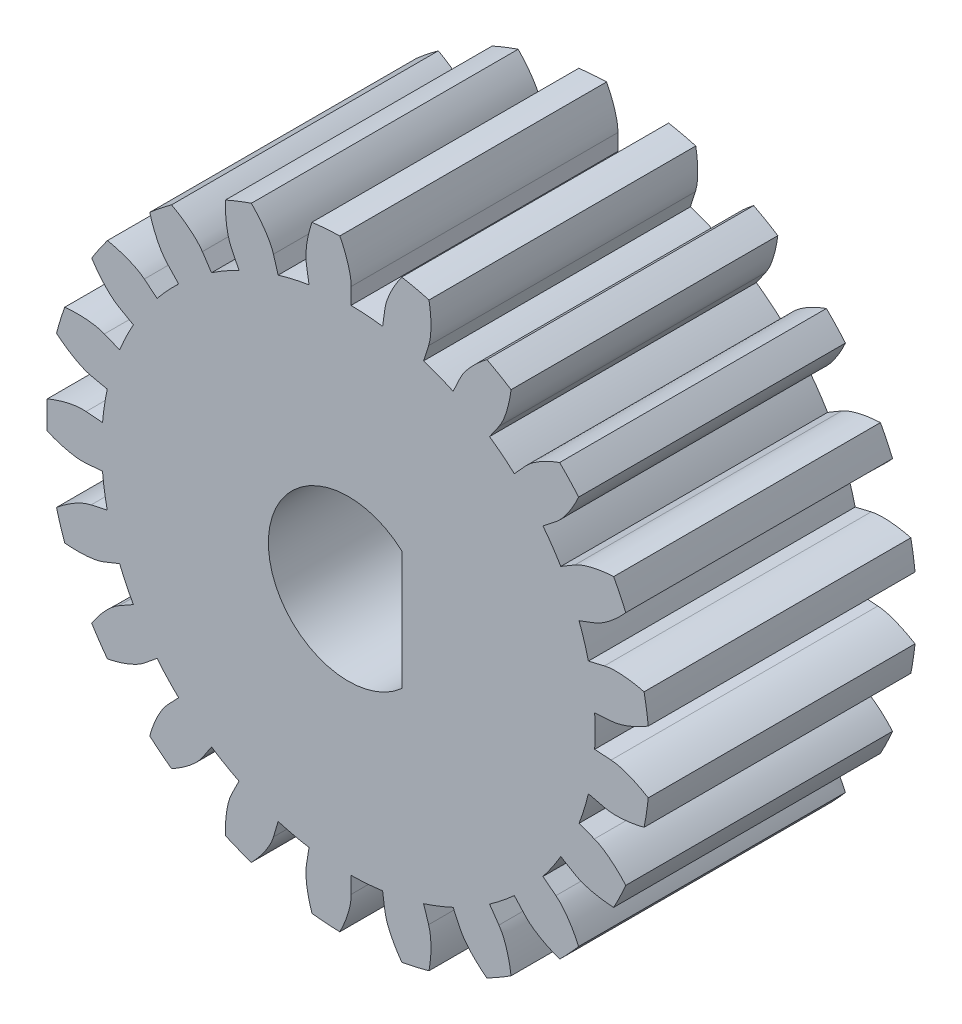
SolidWorks part; units mm, degrees
ref_plane "前视基准面" through (0, 0, 0) normal (0, 0, 1) x (1, 0, 0)
ref_plane "上视基准面" through (0, 0, 0) normal (0, 1, 0) x (1, 0, 0)
ref_plane "右视基准面" through (0, 0, 0) normal (1, 0, 0) x (0, 0, -1)
other "Configuration Table"
sketch "草图1" plane through (0, 0, 0) normal (0, 0, 1) x (1, 0, 0)
  line L0 (0, 0) -> (5.25, 0) construction
  line L1 (0, 0) -> (5.2353, 0.3923) construction
  line L2 (0, 0) -> (4.9232, 0.3169)
  line L3 (5.2353, 0.3923) -> (5.2353, -0.3923) construction
  line L4 (0, 0) -> (4.9232, -0.3169)
  circle A0 centre (0, 0) radius 5.75
  circle A1 centre (0, 0) radius 5.25 construction
  circle A2 centre (0, 0) radius 4.625
  circle A3 centre (0, 0) radius 4.9334 construction
  circle A4 centre (0, 0) radius 1.475
  spline S0 degree 4 poles (4.9232, 0.3169) (4.9607, 0.3193) (5.065, 0.3339) (5.2581, 0.3925) (5.555, 0.5296) (5.9082, 0.7653) (6.3141, 1.1289) (6.7208, 1.6221) (7.0851, 2.222) (7.4595, 3.0902) (7.6869, 4.0103) (7.7831, 4.9894) (7.7375, 6.1592) (7.5421, 7.3154) (7.1213, 8.6118) (6.437, 9.9622) (5.566, 11.1996) (4.5364, 12.3078) (3.3742, 13.2753) (2.1035, 14.0945) (0.7466, 14.7607) (-0.4976, 15.2081) (-1.5022, 15.4709) (-2.2418, 15.6171) (-2.7079, 15.6926) (-3.0798, 15.7435) (-3.4583, 15.7849) (-3.8273, 15.8169) (-4.1819, 15.8376) (-4.4716, 15.8494) (-4.8011, 15.8553) (-5.0151, 15.8558) (-5.3597, 15.8515) (-5.6291, 15.8407) (-5.9536, 15.8242) (-6.2447, 15.8018) (-6.5555, 15.7736) (-6.8526, 15.7397) (-7.0823, 15.71) (-7.2316, 15.6883) (-7.3069, 15.677) knots 0 0 0 0 0 0.005604 0.015718 0.02996 0.048734 0.068727 0.096889 0.125051 0.153212 0.209535 0.237696 0.271429 0.327752 0.384075 0.440398 0.496721 0.553044 0.609367 0.66569 0.722013 0.778336 0.806497 0.820578 0.834659 0.84874 0.86282 0.876901 0.890982 0.900036 0.909091 0.920455 0.931818 0.943182 0.954545 0.965909 0.977273 0.988636 1 1 1 1 1 construction
  spline S1 degree 4 poles (4.9232, 0.3169) (4.9607, 0.3193) (5.065, 0.3339) (5.2581, 0.3925) (5.555, 0.5296) (5.9082, 0.7653) (6.3141, 1.1289) (6.7208, 1.6221) (7.0851, 2.222) (7.4595, 3.0902) (7.6869, 4.0103) (7.7831, 4.9894) (7.7375, 6.1592) (7.5421, 7.3154) (7.1213, 8.6118) (6.437, 9.9622) (5.566, 11.1996) (4.5364, 12.3078) (3.3742, 13.2753) (2.1035, 14.0945) (0.7466, 14.7607) (-0.4976, 15.2081) (-1.5022, 15.4709) (-2.2418, 15.6171) (-2.7079, 15.6926) (-3.0798, 15.7435) (-3.4583, 15.7849) (-3.8273, 15.8169) (-4.1819, 15.8376) (-4.4716, 15.8494) (-4.7152, 15.8537) (-4.8263, 15.8548) (-4.8814, 15.855) knots 0 0 0 0 0 0.005604 0.015718 0.02996 0.048734 0.068727 0.096889 0.125051 0.153212 0.209535 0.237696 0.271429 0.327752 0.384075 0.440398 0.496721 0.553044 0.609367 0.66569 0.722013 0.778336 0.806497 0.820578 0.834659 0.84874 0.86282 0.876901 0.890982 0.900036 0.909091 0.909091 0.909091 0.909091 0.909091
  spline S2 degree 4 poles (4.9232, -0.3169) (4.9607, -0.3193) (5.065, -0.3339) (5.2581, -0.3925) (5.555, -0.5296) (5.9082, -0.7653) (6.3141, -1.1289) (6.7208, -1.6221) (7.0851, -2.222) (7.4595, -3.0902) (7.6869, -4.0103) (7.7831, -4.9894) (7.7375, -6.1592) (7.5421, -7.3154) (7.1213, -8.6118) (6.437, -9.9622) (5.566, -11.1996) (4.5364, -12.3078) (3.3742, -13.2753) (2.1035, -14.0945) (0.7466, -14.7607) (-0.4976, -15.2081) (-1.5022, -15.4709) (-2.2418, -15.6171) (-2.7079, -15.6926) (-3.0798, -15.7435) (-3.4583, -15.7849) (-3.8273, -15.8169) (-4.1819, -15.8376) (-4.4716, -15.8494) (-4.8011, -15.8553) (-5.0151, -15.8558) (-5.3597, -15.8515) (-5.6291, -15.8407) (-5.9536, -15.8242) (-6.2447, -15.8018) (-6.5555, -15.7736) (-6.8526, -15.7397) (-7.0823, -15.71) (-7.2316, -15.6883) (-7.3069, -15.677) knots 0 0 0 0 0 0.005604 0.015718 0.02996 0.048734 0.068727 0.096889 0.125051 0.153212 0.209535 0.237696 0.271429 0.327752 0.384075 0.440398 0.496721 0.553044 0.609367 0.66569 0.722013 0.778336 0.806497 0.820578 0.834659 0.84874 0.86282 0.876901 0.890982 0.900036 0.909091 0.920455 0.931818 0.943182 0.954545 0.965909 0.977273 0.988636 1 1 1 1 1 construction
  spline S3 degree 4 poles (4.9232, -0.3169) (4.9607, -0.3193) (5.065, -0.3339) (5.2581, -0.3925) (5.555, -0.5296) (5.9082, -0.7653) (6.3141, -1.1289) (6.7208, -1.6221) (7.0851, -2.222) (7.4595, -3.0902) (7.6869, -4.0103) (7.7831, -4.9894) (7.7375, -6.1592) (7.5421, -7.3154) (7.1213, -8.6118) (6.437, -9.9622) (5.566, -11.1996) (4.5364, -12.3078) (3.3742, -13.2753) (2.1035, -14.0945) (0.7466, -14.7607) (-0.4976, -15.2081) (-1.5022, -15.4709) (-2.2418, -15.6171) (-2.7079, -15.6926) (-3.0798, -15.7435) (-3.4583, -15.7849) (-3.8273, -15.8169) (-4.1819, -15.8376) (-4.4716, -15.8494) (-4.7152, -15.8537) (-4.8263, -15.8548) (-4.8814, -15.855) knots 0 0 0 0 0 0.005604 0.015718 0.02996 0.048734 0.068727 0.096889 0.125051 0.153212 0.209535 0.237696 0.271429 0.327752 0.384075 0.440398 0.496721 0.553044 0.609367 0.66569 0.722013 0.778336 0.806497 0.820578 0.834659 0.84874 0.86282 0.876901 0.890982 0.900036 0.909091 0.909091 0.909091 0.909091 0.909091
  point P15 (5.2353, 0)
  dimension "齿顶圆直径" = 11.5
  dimension "分度圆直径" = 10.5
  dimension "齿根圆直径" = 9.25
  dimension "基圆直径" = 9.8668
  dimension "内孔直径" = 2.95
  dimension "渐近线镜像线夹角" = 4.286
extrude "凸台-拉伸1" add sketch "草图1" along normal blind 5 contours A0 | A4
extrude "切除-拉伸1" cut sketch "草图1<3>" along normal through all contours A2 S3 A0 S1 region at (5.2601, 0, 0)
sketch "草图1<3>" plane through (0, 0, 0) normal (0, 0, 1) x (1, 0, 0) same geometry as "草图1"
pattern_circular "阵列(圆周)1" count 21 every 17.143 about axis through (0, 0, 5) along (0, 0, 1) of "切除-拉伸1"
sketch "草图2" plane through (0, 0, 5) normal (0, 0, 1) x (1, 0, 0)
  circle A0 centre (0, 0) radius 1.475
extrude "凸台-拉伸2" add sketch "草图2" against normal through all
sketch "草图3" plane through (0, 0, 5) normal (0, 0, 1) x (1, 0, 0)
  line L0 (1, 1.118) -> (1, -1.118)
  circle A0 centre (0, 0) radius 1.5
  dimension "D2" = 3
  dimension "D1" = 1
extrude "切除-拉伸2" cut sketch "草图3" against normal through all contours L0 A0 region at (-0.148, 0, 5)
sketch "草图4" plane through (0, 0, 5) normal (0, 0, 1) x (1, 0, 0)
  circle A0 centre (0, 0) radius 5.65
  arc A1 (3.0602, 4.868) -> (2.6857, 5.0842) centre (0, 0) ccw construction
  point P5 (0, 0)
  dimension "D1" = 0.1
extrude "切除-拉伸3" cut sketch "草图4" against normal through all flip side to cut
equation "\"m\"= 0.5'模数"
equation "\"z\"= 21'齿数"
equation "\"a\"= 20度'压力角"
equation "\"d\"= \"m\" * \"z\"'分度圆直径"
equation "\"da\"= ( \"z\" + 2 ) * \"m\"'齿顶圆直径"
equation "\"df\"= ( \"z\" - 2.5 ) * \"m\"'齿根圆直径"
equation "\"s\"= 0.5 * PI * \"m\"'分度圆齿厚"
equation "\"r\"= 0.38 * \"m\"'齿根圆角"
equation "\"B\"= 0.3 * \"d\"'齿厚"
equation "\"db\"= \"m\" * \"z\" * cos ( \"a\" )'基圆直径"
equation "\"rb\"= \"db\" / 2'基圆半径"
equation "\"齿顶圆直径@草图1\"= \"da\""
equation "\"分度圆直径@草图1\"= \"d\""
equation "\"齿根圆直径@草图1\"= \"df\""
equation "\"基圆直径@草图1\"= \"db\""
equation "\"渐近线镜像线夹角@草图1\"= 360 / 4 / \"z\""
equation "\"h\"= 5'齿轮厚度"
equation "\"ir\"= 2.95'内孔直径"
equation "\"内孔直径@草图1\"= \"ir\""
equation "\"齿轮厚@凸台-拉伸1\"= \"h\""
equation "\"齿轮夹角@阵列(圆周)1\"= 360 / \"z\""
equation "\"齿数@阵列(圆周)1\"= \"z\""
